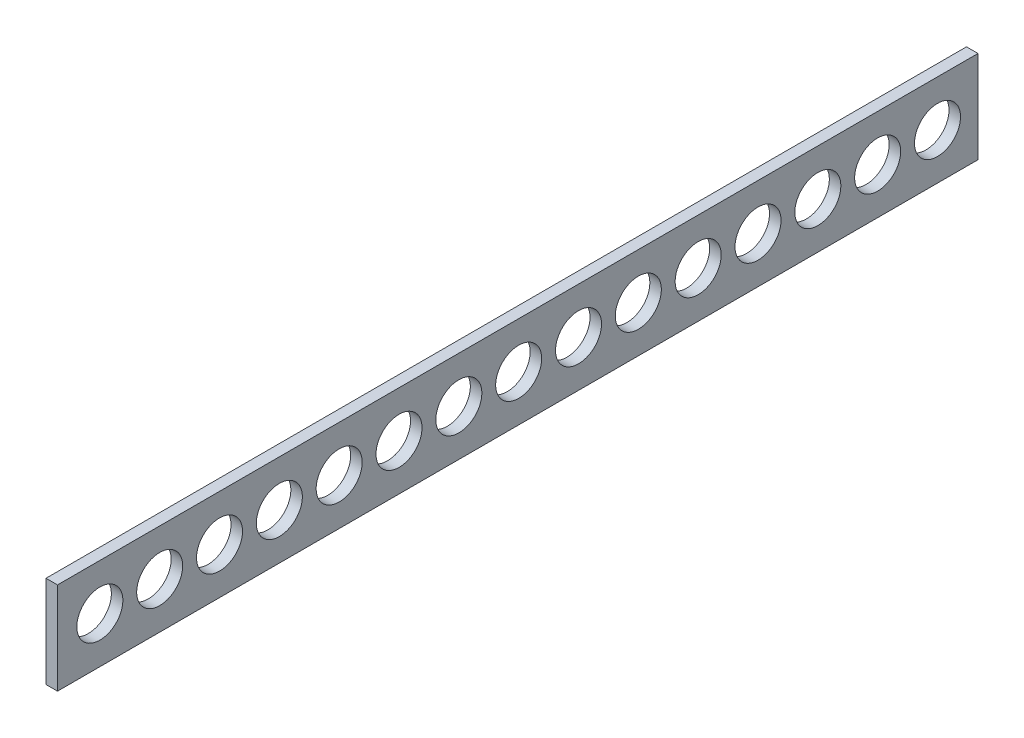
SolidWorks part; units mm, degrees
ref_plane "Front Plane" through (0, 0, 0) normal (0, 0, 1) x (1, 0, 0)
ref_plane "Top Plane" through (0, 0, 0) normal (0, 1, 0) x (1, 0, 0)
ref_plane "Right Plane" through (0, 0, 0) normal (1, 0, 0) x (0, 0, -1)
sketch "Sketch1" plane through (0, 0, 0) normal (1, 0, 0) x (0, 0, -1)
  line L0 (0, 25.4) -> (508, 25.4) construction
  line L1 (0, 0) -> (508, 0)
  line L2 (0, 0) -> (0, 50.8)
  line L3 (0, 50.8) -> (508, 50.8)
  line L4 (508, 0) -> (508, 50.8)
  circle A0 centre (23.3708, 25.4) radius 12.7
  circle A1 centre (56.3908, 25.4) radius 12.7
  circle A2 centre (89.4108, 25.4) radius 12.7
  circle A3 centre (122.4308, 25.4) radius 12.7
  circle A4 centre (155.4508, 25.4) radius 12.7
  circle A5 centre (188.4708, 25.4) radius 12.7
  circle A6 centre (221.4908, 25.4) radius 12.7
  circle A7 centre (254.5108, 25.4) radius 12.7
  circle A8 centre (287.5308, 25.4) radius 12.7
  circle A9 centre (320.5508, 25.4) radius 12.7
  circle A10 centre (353.5708, 25.4) radius 12.7
  circle A11 centre (386.5908, 25.4) radius 12.7
  circle A12 centre (419.6108, 25.4) radius 12.7
  circle A13 centre (452.6308, 25.4) radius 12.7
  circle A14 centre (485.6508, 25.4) radius 12.7
  dimension "D2" = 25.4
  dimension "D1" = 508
  dimension "D4" = 50.8
  dimension "D3" = 15
extrude "Boss-Extrude1" add sketch "Sketch1" along normal blind 6.35
